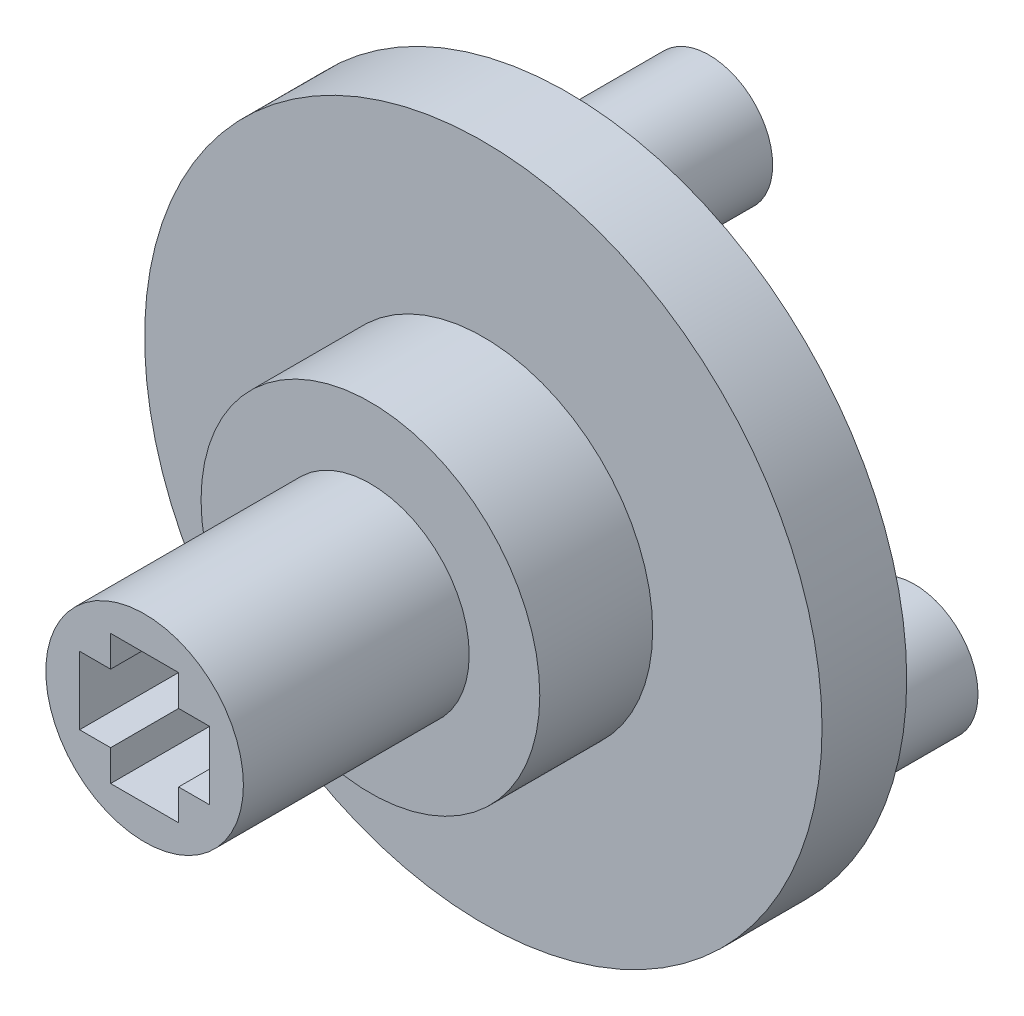
SolidWorks part; units mm, degrees
ref_plane "前视基准面" through (0, 0, 0) normal (0, 0, 1) x (1, 0, 0)
ref_plane "上视基准面" through (0, 0, 0) normal (0, 1, 0) x (1, 0, 0)
ref_plane "右视基准面" through (0, 0, 0) normal (1, 0, 0) x (0, 0, -1)
other "Configuration Table"
sketch "草图1" plane through (0, 0, 0) normal (0, 0, 1) x (1, 0, 0)
  circle A0 centre (0, 0) radius 8.4 construction
  circle A1 centre (0, 0) radius 2
  circle A2 centre (0, 8.4) radius 2.25
  circle A3 centre (7.2746, -4.2) radius 2.25
  circle A4 centre (-7.2746, -4.2) radius 2.25
  circle A5 centre (0, 0) radius 12
  circle A6 centre (0, 0) radius 6
  point P12 (0, 0)
  dimension "D1" = 16.8
  dimension "D2" = 4.5
  dimension "D3" = 4
  dimension "D5" = 24
  dimension "D6" = 12
  dimension "D4" = 3
extrude "凸台-拉伸1" add sketch "草图1" along normal blind 3 contours A1 | A5 region at (0, 0, 0)
extrude "凸台-拉伸2" add sketch "草图1<3>" against normal blind 5 contours A0 A2 | A0 A2 | A0 A3 | A0 A3 | A0 A4 | A0 A4 region at (0, 8.4, 0) region at (7.2746, -4.2, 0) region at (-7.2746, -4.2, 0)
sketch "草图1<3>" plane through (0, 0, 0) normal (0, 0, 1) x (1, 0, 0) same geometry as "草图1"
extrude "凸台-拉伸3" add sketch "草图1<4>" along normal blind 3 from surface contours A6 A1 region at (-5.8303, 0, 0) starting at face at (12, 0, 3)
sketch "草图1<4>" plane through (0, 0, 0) normal (0, 0, 1) x (1, 0, 0) same geometry as "草图1"
extrude "凸台-拉伸5" add sketch "草图1<5>" along normal blind 1 from surface contours A6 starting at face at (6, 0, 6)
sketch "草图1<5>" plane through (0, 0, 0) normal (0, 0, 1) x (1, 0, 0) same geometry as "草图1"
sketch "草图2" plane through (0, 0, 7) normal (0, 0, 1) x (1, 0, 0)
  line L1 (-1.2043, -2.3043) -> (1.2043, -2.3043)
  line L2 (-1.2043, -2.3043) -> (-1.2043, 2.3043)
  line L3 (-1.2043, 2.3043) -> (1.2043, 2.3043)
  line L4 (1.2043, -2.3043) -> (1.2043, 2.3043)
  line L5 (-1.2043, -2.3043) -> (1.2043, 2.3043) construction
  line L6 (-1.2043, 2.3043) -> (1.2043, -2.3043) construction
  line L7 (-2.3043, -1.2043) -> (2.3043, -1.2043)
  line L8 (-2.3043, -1.2043) -> (-2.3043, 1.2043)
  line L9 (-2.3043, 1.2043) -> (2.3043, 1.2043)
  line L10 (2.3043, -1.2043) -> (2.3043, 1.2043)
  line L11 (-2.3043, -1.2043) -> (2.3043, 1.2043) construction
  line L12 (-2.3043, 1.2043) -> (2.3043, -1.2043) construction
  circle A0 centre (0, 0) radius 3.5
  circle A1 centre (0, 0) radius 2.6
  dimension "D1" = 7
  dimension "D2" = 5.2
  dimension "D3" = 1.1
extrude "凸台-拉伸4" add sketch "草图2" along normal blind 8 contours L3 A1 | L2 A1 L9 | A1 | L8 A1 | A0 | L7 A1 L2 | L1 A1 | L4 A1 L7 | L10 A1 | L9 A1 L4 region at (-1.6079, -1.6079, 7) region at (0, -2.4232, 7) region at (1.6079, -1.6079, 7) region at (-2.4232, 0, 7) region at (2.4232, 0, 7) region at (-1.6079, 1.6079, 7) region at (1.6079, 1.6079, 7) region at (0, 2.4232, 7) region at (-3.401, 0, 7)
